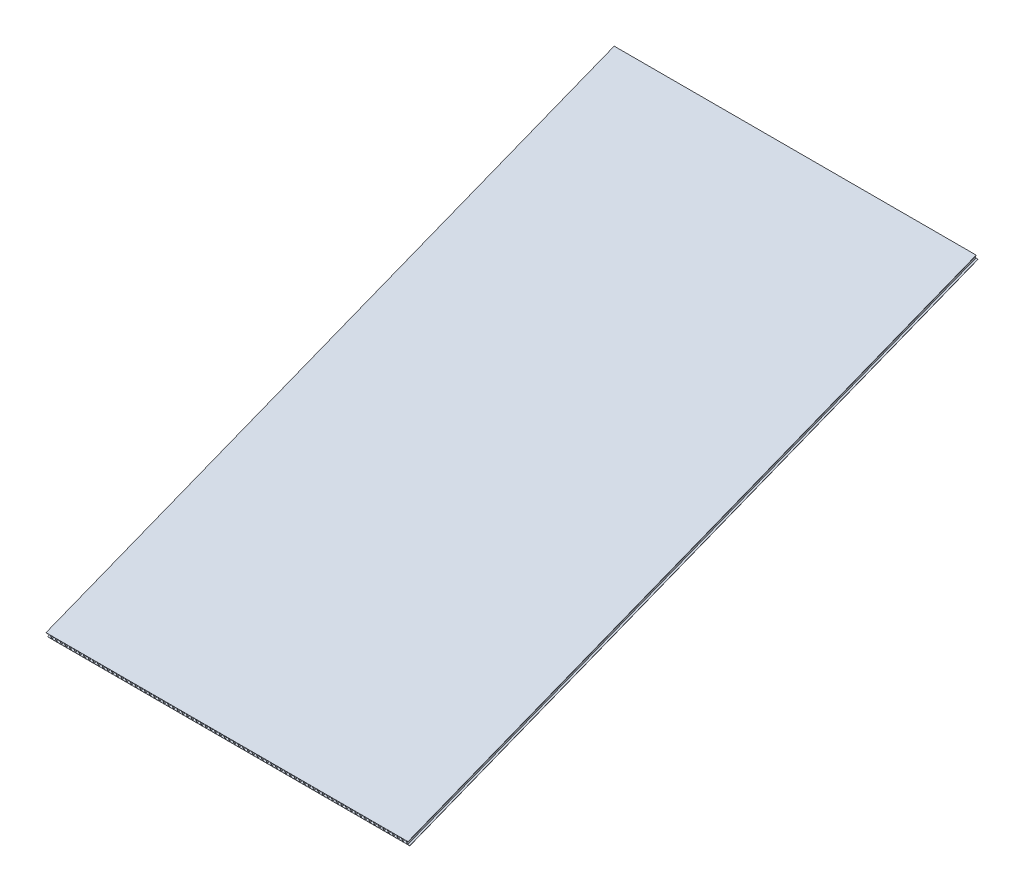
SolidWorks part; units mm, degrees
ref_plane "Front Plane" through (0, 0, 0) normal (0, 0, 1) x (1, 0, 0)
ref_plane "Top Plane" through (0, 0, 0) normal (0, 1, 0) x (1, 0, 0)
ref_plane "Right Plane" through (0, 0, 0) normal (1, 0, 0) x (0, 0, -1)
sketch "Sketch1" plane through (0, 0, 0) normal (1, 0, 0) x (0, 0, -1)
  line L0 (0, 0) -> (-1566.3458, 0) construction
  line L1 (0, 617) -> (-1566.3458, 0)
  line L2 (0, 0) -> (0, 617) construction
  dimension "D1" = 617
  dimension "D2" = 21.5
extrude "Extrude-Thin1" add sketch "Sketch1" along normal blind 1810 thin thin type one direction wall 10
sketch "Sketch2" plane through (0, 82.8774, -210.3965) normal (0, 0.3665, -0.9304) x (-1, 0, 0)
  line L0 (-1810, 584.0676) -> (-1810, 574.0676) construction
  line L1 (-1809.5, 583.5676) -> (-1800.5, 583.5676)
  line L2 (-1809.5, 583.5676) -> (-1809.5, 574.5676)
  line L3 (-1809.5, 574.5676) -> (-1800.5, 574.5676)
  line L4 (-1800.5, 583.5676) -> (-1800.5, 574.5676)
  line L5 (-1810, 584.0676) -> (0, 584.0676) construction
  line L6 (-1810, 574.0676) -> (0, 574.0676) construction
  line L7 (-1791, 583.5676) -> (-1791, 574.5676)
  line L8 (-1800, 574.5676) -> (-1791, 574.5676)
  line L9 (-1800, 583.5676) -> (-1800, 574.5676)
  line L10 (-1800, 583.5676) -> (-1791, 583.5676)
  line L11 (-1781.5, 583.5676) -> (-1781.5, 574.5676)
  line L12 (-1790.5, 574.5676) -> (-1781.5, 574.5676)
  line L13 (-1790.5, 583.5676) -> (-1790.5, 574.5676)
  line L14 (-1790.5, 583.5676) -> (-1781.5, 583.5676)
  line L15 (-1772, 583.5676) -> (-1772, 574.5676)
  line L16 (-1781, 574.5676) -> (-1772, 574.5676)
  line L17 (-1781, 583.5676) -> (-1781, 574.5676)
  line L18 (-1781, 583.5676) -> (-1772, 583.5676)
  line L19 (-1762.5, 583.5676) -> (-1762.5, 574.5676)
  line L20 (-1771.5, 574.5676) -> (-1762.5, 574.5676)
  line L21 (-1771.5, 583.5676) -> (-1771.5, 574.5676)
  line L22 (-1771.5, 583.5676) -> (-1762.5, 583.5676)
  line L23 (-1753, 583.5676) -> (-1753, 574.5676)
  line L24 (-1762, 574.5676) -> (-1753, 574.5676)
  line L25 (-1762, 583.5676) -> (-1762, 574.5676)
  line L26 (-1762, 583.5676) -> (-1753, 583.5676)
  line L27 (-1743.5, 583.5676) -> (-1743.5, 574.5676)
  line L28 (-1752.5, 574.5676) -> (-1743.5, 574.5676)
  line L29 (-1752.5, 583.5676) -> (-1752.5, 574.5676)
  line L30 (-1752.5, 583.5676) -> (-1743.5, 583.5676)
  line L31 (-1734, 583.5676) -> (-1734, 574.5676)
  line L32 (-1743, 574.5676) -> (-1734, 574.5676)
  line L33 (-1743, 583.5676) -> (-1743, 574.5676)
  line L34 (-1743, 583.5676) -> (-1734, 583.5676)
  line L35 (-1724.5, 583.5676) -> (-1724.5, 574.5676)
  line L36 (-1733.5, 574.5676) -> (-1724.5, 574.5676)
  line L37 (-1733.5, 583.5676) -> (-1733.5, 574.5676)
  line L38 (-1733.5, 583.5676) -> (-1724.5, 583.5676)
  line L39 (-1715, 583.5676) -> (-1715, 574.5676)
  line L40 (-1724, 574.5676) -> (-1715, 574.5676)
  line L41 (-1724, 583.5676) -> (-1724, 574.5676)
  line L42 (-1724, 583.5676) -> (-1715, 583.5676)
  line L43 (-1705.5, 583.5676) -> (-1705.5, 574.5676)
  line L44 (-1714.5, 574.5676) -> (-1705.5, 574.5676)
  line L45 (-1714.5, 583.5676) -> (-1714.5, 574.5676)
  line L46 (-1714.5, 583.5676) -> (-1705.5, 583.5676)
  line L47 (-1696, 583.5676) -> (-1696, 574.5676)
  line L48 (-1705, 574.5676) -> (-1696, 574.5676)
  line L49 (-1705, 583.5676) -> (-1705, 574.5676)
  line L50 (-1705, 583.5676) -> (-1696, 583.5676)
  line L51 (-1686.5, 583.5676) -> (-1686.5, 574.5676)
  line L52 (-1695.5, 574.5676) -> (-1686.5, 574.5676)
  line L53 (-1695.5, 583.5676) -> (-1695.5, 574.5676)
  line L54 (-1695.5, 583.5676) -> (-1686.5, 583.5676)
  line L55 (-1677, 583.5676) -> (-1677, 574.5676)
  line L56 (-1686, 574.5676) -> (-1677, 574.5676)
  line L57 (-1686, 583.5676) -> (-1686, 574.5676)
  line L58 (-1686, 583.5676) -> (-1677, 583.5676)
  line L59 (-1667.5, 583.5676) -> (-1667.5, 574.5676)
  line L60 (-1676.5, 574.5676) -> (-1667.5, 574.5676)
  line L61 (-1676.5, 583.5676) -> (-1676.5, 574.5676)
  line L62 (-1676.5, 583.5676) -> (-1667.5, 583.5676)
  line L63 (-1658, 583.5676) -> (-1658, 574.5676)
  line L64 (-1667, 574.5676) -> (-1658, 574.5676)
  line L65 (-1667, 583.5676) -> (-1667, 574.5676)
  line L66 (-1667, 583.5676) -> (-1658, 583.5676)
  line L67 (-1648.5, 583.5676) -> (-1648.5, 574.5676)
  line L68 (-1657.5, 574.5676) -> (-1648.5, 574.5676)
  line L69 (-1657.5, 583.5676) -> (-1657.5, 574.5676)
  line L70 (-1657.5, 583.5676) -> (-1648.5, 583.5676)
  line L71 (-1639, 583.5676) -> (-1639, 574.5676)
  line L72 (-1648, 574.5676) -> (-1639, 574.5676)
  line L73 (-1648, 583.5676) -> (-1648, 574.5676)
  line L74 (-1648, 583.5676) -> (-1639, 583.5676)
  line L75 (-1629.5, 583.5676) -> (-1629.5, 574.5676)
  line L76 (-1638.5, 574.5676) -> (-1629.5, 574.5676)
  line L77 (-1638.5, 583.5676) -> (-1638.5, 574.5676)
  line L78 (-1638.5, 583.5676) -> (-1629.5, 583.5676)
  line L79 (-1620, 583.5676) -> (-1620, 574.5676)
  line L80 (-1629, 574.5676) -> (-1620, 574.5676)
  line L81 (-1629, 583.5676) -> (-1629, 574.5676)
  line L82 (-1629, 583.5676) -> (-1620, 583.5676)
  line L83 (-1610.5, 583.5676) -> (-1610.5, 574.5676)
  line L84 (-1619.5, 574.5676) -> (-1610.5, 574.5676)
  line L85 (-1619.5, 583.5676) -> (-1619.5, 574.5676)
  line L86 (-1619.5, 583.5676) -> (-1610.5, 583.5676)
  line L87 (-1601, 583.5676) -> (-1601, 574.5676)
  line L88 (-1610, 574.5676) -> (-1601, 574.5676)
  line L89 (-1610, 583.5676) -> (-1610, 574.5676)
  line L90 (-1610, 583.5676) -> (-1601, 583.5676)
  line L91 (-1591.5, 583.5676) -> (-1591.5, 574.5676)
  line L92 (-1600.5, 574.5676) -> (-1591.5, 574.5676)
  line L93 (-1600.5, 583.5676) -> (-1600.5, 574.5676)
  line L94 (-1600.5, 583.5676) -> (-1591.5, 583.5676)
  line L95 (-1582, 583.5676) -> (-1582, 574.5676)
  line L96 (-1591, 574.5676) -> (-1582, 574.5676)
  line L97 (-1591, 583.5676) -> (-1591, 574.5676)
  line L98 (-1591, 583.5676) -> (-1582, 583.5676)
  line L99 (-1572.5, 583.5676) -> (-1572.5, 574.5676)
  line L100 (-1581.5, 574.5676) -> (-1572.5, 574.5676)
  line L101 (-1581.5, 583.5676) -> (-1581.5, 574.5676)
  line L102 (-1581.5, 583.5676) -> (-1572.5, 583.5676)
  line L103 (-1563, 583.5676) -> (-1563, 574.5676)
  line L104 (-1572, 574.5676) -> (-1563, 574.5676)
  line L105 (-1572, 583.5676) -> (-1572, 574.5676)
  line L106 (-1572, 583.5676) -> (-1563, 583.5676)
  line L107 (-1553.5, 583.5676) -> (-1553.5, 574.5676)
  line L108 (-1562.5, 574.5676) -> (-1553.5, 574.5676)
  line L109 (-1562.5, 583.5676) -> (-1562.5, 574.5676)
  line L110 (-1562.5, 583.5676) -> (-1553.5, 583.5676)
  line L111 (-1544, 583.5676) -> (-1544, 574.5676)
  line L112 (-1553, 574.5676) -> (-1544, 574.5676)
  line L113 (-1553, 583.5676) -> (-1553, 574.5676)
  line L114 (-1553, 583.5676) -> (-1544, 583.5676)
  line L115 (-1534.5, 583.5676) -> (-1534.5, 574.5676)
  line L116 (-1543.5, 574.5676) -> (-1534.5, 574.5676)
  line L117 (-1543.5, 583.5676) -> (-1543.5, 574.5676)
  line L118 (-1543.5, 583.5676) -> (-1534.5, 583.5676)
  line L119 (-1525, 583.5676) -> (-1525, 574.5676)
  line L120 (-1534, 574.5676) -> (-1525, 574.5676)
  line L121 (-1534, 583.5676) -> (-1534, 574.5676)
  line L122 (-1534, 583.5676) -> (-1525, 583.5676)
  line L123 (-1515.5, 583.5676) -> (-1515.5, 574.5676)
  line L124 (-1524.5, 574.5676) -> (-1515.5, 574.5676)
  line L125 (-1524.5, 583.5676) -> (-1524.5, 574.5676)
  line L126 (-1524.5, 583.5676) -> (-1515.5, 583.5676)
  line L127 (-1506, 583.5676) -> (-1506, 574.5676)
  line L128 (-1515, 574.5676) -> (-1506, 574.5676)
  line L129 (-1515, 583.5676) -> (-1515, 574.5676)
  line L130 (-1515, 583.5676) -> (-1506, 583.5676)
  line L131 (-1496.5, 583.5676) -> (-1496.5, 574.5676)
  line L132 (-1505.5, 574.5676) -> (-1496.5, 574.5676)
  line L133 (-1505.5, 583.5676) -> (-1505.5, 574.5676)
  line L134 (-1505.5, 583.5676) -> (-1496.5, 583.5676)
  line L135 (-1487, 583.5676) -> (-1487, 574.5676)
  line L136 (-1496, 574.5676) -> (-1487, 574.5676)
  line L137 (-1496, 583.5676) -> (-1496, 574.5676)
  line L138 (-1496, 583.5676) -> (-1487, 583.5676)
  line L139 (-1477.5, 583.5676) -> (-1477.5, 574.5676)
  line L140 (-1486.5, 574.5676) -> (-1477.5, 574.5676)
  line L141 (-1486.5, 583.5676) -> (-1486.5, 574.5676)
  line L142 (-1486.5, 583.5676) -> (-1477.5, 583.5676)
  line L143 (-1468, 583.5676) -> (-1468, 574.5676)
  line L144 (-1477, 574.5676) -> (-1468, 574.5676)
  line L145 (-1477, 583.5676) -> (-1477, 574.5676)
  line L146 (-1477, 583.5676) -> (-1468, 583.5676)
  line L147 (-1458.5, 583.5676) -> (-1458.5, 574.5676)
  line L148 (-1467.5, 574.5676) -> (-1458.5, 574.5676)
  line L149 (-1467.5, 583.5676) -> (-1467.5, 574.5676)
  line L150 (-1467.5, 583.5676) -> (-1458.5, 583.5676)
  line L151 (-1449, 583.5676) -> (-1449, 574.5676)
  line L152 (-1458, 574.5676) -> (-1449, 574.5676)
  line L153 (-1458, 583.5676) -> (-1458, 574.5676)
  line L154 (-1458, 583.5676) -> (-1449, 583.5676)
  line L155 (-1439.5, 583.5676) -> (-1439.5, 574.5676)
  line L156 (-1448.5, 574.5676) -> (-1439.5, 574.5676)
  line L157 (-1448.5, 583.5676) -> (-1448.5, 574.5676)
  line L158 (-1448.5, 583.5676) -> (-1439.5, 583.5676)
  line L159 (-1430, 583.5676) -> (-1430, 574.5676)
  line L160 (-1439, 574.5676) -> (-1430, 574.5676)
  line L161 (-1439, 583.5676) -> (-1439, 574.5676)
  line L162 (-1439, 583.5676) -> (-1430, 583.5676)
  line L163 (-1420.5, 583.5676) -> (-1420.5, 574.5676)
  line L164 (-1429.5, 574.5676) -> (-1420.5, 574.5676)
  line L165 (-1429.5, 583.5676) -> (-1429.5, 574.5676)
  line L166 (-1429.5, 583.5676) -> (-1420.5, 583.5676)
  line L167 (-1411, 583.5676) -> (-1411, 574.5676)
  line L168 (-1420, 574.5676) -> (-1411, 574.5676)
  line L169 (-1420, 583.5676) -> (-1420, 574.5676)
  line L170 (-1420, 583.5676) -> (-1411, 583.5676)
  line L171 (-1401.5, 583.5676) -> (-1401.5, 574.5676)
  line L172 (-1410.5, 574.5676) -> (-1401.5, 574.5676)
  line L173 (-1410.5, 583.5676) -> (-1410.5, 574.5676)
  line L174 (-1410.5, 583.5676) -> (-1401.5, 583.5676)
  line L175 (-1392, 583.5676) -> (-1392, 574.5676)
  line L176 (-1401, 574.5676) -> (-1392, 574.5676)
  line L177 (-1401, 583.5676) -> (-1401, 574.5676)
  line L178 (-1401, 583.5676) -> (-1392, 583.5676)
  line L179 (-1382.5, 583.5676) -> (-1382.5, 574.5676)
  line L180 (-1391.5, 574.5676) -> (-1382.5, 574.5676)
  line L181 (-1391.5, 583.5676) -> (-1391.5, 574.5676)
  line L182 (-1391.5, 583.5676) -> (-1382.5, 583.5676)
  line L183 (-1373, 583.5676) -> (-1373, 574.5676)
  line L184 (-1382, 574.5676) -> (-1373, 574.5676)
  line L185 (-1382, 583.5676) -> (-1382, 574.5676)
  line L186 (-1382, 583.5676) -> (-1373, 583.5676)
  line L187 (-1363.5, 583.5676) -> (-1363.5, 574.5676)
  line L188 (-1372.5, 574.5676) -> (-1363.5, 574.5676)
  line L189 (-1372.5, 583.5676) -> (-1372.5, 574.5676)
  line L190 (-1372.5, 583.5676) -> (-1363.5, 583.5676)
  line L191 (-1354, 583.5676) -> (-1354, 574.5676)
  line L192 (-1363, 574.5676) -> (-1354, 574.5676)
  line L193 (-1363, 583.5676) -> (-1363, 574.5676)
  line L194 (-1363, 583.5676) -> (-1354, 583.5676)
  line L195 (-1344.5, 583.5676) -> (-1344.5, 574.5676)
  line L196 (-1353.5, 574.5676) -> (-1344.5, 574.5676)
  line L197 (-1353.5, 583.5676) -> (-1353.5, 574.5676)
  line L198 (-1353.5, 583.5676) -> (-1344.5, 583.5676)
  line L199 (-1335, 583.5676) -> (-1335, 574.5676)
  line L200 (-1344, 574.5676) -> (-1335, 574.5676)
  line L201 (-1344, 583.5676) -> (-1344, 574.5676)
  line L202 (-1344, 583.5676) -> (-1335, 583.5676)
  line L203 (-1325.5, 583.5676) -> (-1325.5, 574.5676)
  line L204 (-1334.5, 574.5676) -> (-1325.5, 574.5676)
  line L205 (-1334.5, 583.5676) -> (-1334.5, 574.5676)
  line L206 (-1334.5, 583.5676) -> (-1325.5, 583.5676)
  line L207 (-1316, 583.5676) -> (-1316, 574.5676)
  line L208 (-1325, 574.5676) -> (-1316, 574.5676)
  line L209 (-1325, 583.5676) -> (-1325, 574.5676)
  line L210 (-1325, 583.5676) -> (-1316, 583.5676)
  line L211 (-1306.5, 583.5676) -> (-1306.5, 574.5676)
  line L212 (-1315.5, 574.5676) -> (-1306.5, 574.5676)
  line L213 (-1315.5, 583.5676) -> (-1315.5, 574.5676)
  line L214 (-1315.5, 583.5676) -> (-1306.5, 583.5676)
  line L215 (-1297, 583.5676) -> (-1297, 574.5676)
  line L216 (-1306, 574.5676) -> (-1297, 574.5676)
  line L217 (-1306, 583.5676) -> (-1306, 574.5676)
  line L218 (-1306, 583.5676) -> (-1297, 583.5676)
  line L219 (-1287.5, 583.5676) -> (-1287.5, 574.5676)
  line L220 (-1296.5, 574.5676) -> (-1287.5, 574.5676)
  line L221 (-1296.5, 583.5676) -> (-1296.5, 574.5676)
  line L222 (-1296.5, 583.5676) -> (-1287.5, 583.5676)
  line L223 (-1278, 583.5676) -> (-1278, 574.5676)
  line L224 (-1287, 574.5676) -> (-1278, 574.5676)
  line L225 (-1287, 583.5676) -> (-1287, 574.5676)
  line L226 (-1287, 583.5676) -> (-1278, 583.5676)
  line L227 (-1268.5, 583.5676) -> (-1268.5, 574.5676)
  line L228 (-1277.5, 574.5676) -> (-1268.5, 574.5676)
  line L229 (-1277.5, 583.5676) -> (-1277.5, 574.5676)
  line L230 (-1277.5, 583.5676) -> (-1268.5, 583.5676)
  line L231 (-1259, 583.5676) -> (-1259, 574.5676)
  line L232 (-1268, 574.5676) -> (-1259, 574.5676)
  line L233 (-1268, 583.5676) -> (-1268, 574.5676)
  line L234 (-1268, 583.5676) -> (-1259, 583.5676)
  line L235 (-1249.5, 583.5676) -> (-1249.5, 574.5676)
  line L236 (-1258.5, 574.5676) -> (-1249.5, 574.5676)
  line L237 (-1258.5, 583.5676) -> (-1258.5, 574.5676)
  line L238 (-1258.5, 583.5676) -> (-1249.5, 583.5676)
  line L239 (-1240, 583.5676) -> (-1240, 574.5676)
  line L240 (-1249, 574.5676) -> (-1240, 574.5676)
  line L241 (-1249, 583.5676) -> (-1249, 574.5676)
  line L242 (-1249, 583.5676) -> (-1240, 583.5676)
  line L243 (-1230.5, 583.5676) -> (-1230.5, 574.5676)
  line L244 (-1239.5, 574.5676) -> (-1230.5, 574.5676)
  line L245 (-1239.5, 583.5676) -> (-1239.5, 574.5676)
  line L246 (-1239.5, 583.5676) -> (-1230.5, 583.5676)
  line L247 (-1221, 583.5676) -> (-1221, 574.5676)
  line L248 (-1230, 574.5676) -> (-1221, 574.5676)
  line L249 (-1230, 583.5676) -> (-1230, 574.5676)
  line L250 (-1230, 583.5676) -> (-1221, 583.5676)
  line L251 (-1211.5, 583.5676) -> (-1211.5, 574.5676)
  line L252 (-1220.5, 574.5676) -> (-1211.5, 574.5676)
  line L253 (-1220.5, 583.5676) -> (-1220.5, 574.5676)
  line L254 (-1220.5, 583.5676) -> (-1211.5, 583.5676)
  line L255 (-1202, 583.5676) -> (-1202, 574.5676)
  line L256 (-1211, 574.5676) -> (-1202, 574.5676)
  line L257 (-1211, 583.5676) -> (-1211, 574.5676)
  line L258 (-1211, 583.5676) -> (-1202, 583.5676)
  line L259 (-1192.5, 583.5676) -> (-1192.5, 574.5676)
  line L260 (-1201.5, 574.5676) -> (-1192.5, 574.5676)
  line L261 (-1201.5, 583.5676) -> (-1201.5, 574.5676)
  line L262 (-1201.5, 583.5676) -> (-1192.5, 583.5676)
  line L263 (-1183, 583.5676) -> (-1183, 574.5676)
  line L264 (-1192, 574.5676) -> (-1183, 574.5676)
  line L265 (-1192, 583.5676) -> (-1192, 574.5676)
  line L266 (-1192, 583.5676) -> (-1183, 583.5676)
  line L267 (-1173.5, 583.5676) -> (-1173.5, 574.5676)
  line L268 (-1182.5, 574.5676) -> (-1173.5, 574.5676)
  line L269 (-1182.5, 583.5676) -> (-1182.5, 574.5676)
  line L270 (-1182.5, 583.5676) -> (-1173.5, 583.5676)
  line L271 (-1164, 583.5676) -> (-1164, 574.5676)
  line L272 (-1173, 574.5676) -> (-1164, 574.5676)
  line L273 (-1173, 583.5676) -> (-1173, 574.5676)
  line L274 (-1173, 583.5676) -> (-1164, 583.5676)
  line L275 (-1154.5, 583.5676) -> (-1154.5, 574.5676)
  line L276 (-1163.5, 574.5676) -> (-1154.5, 574.5676)
  line L277 (-1163.5, 583.5676) -> (-1163.5, 574.5676)
  line L278 (-1163.5, 583.5676) -> (-1154.5, 583.5676)
  line L279 (-1145, 583.5676) -> (-1145, 574.5676)
  line L280 (-1154, 574.5676) -> (-1145, 574.5676)
  line L281 (-1154, 583.5676) -> (-1154, 574.5676)
  line L282 (-1154, 583.5676) -> (-1145, 583.5676)
  line L283 (-1135.5, 583.5676) -> (-1135.5, 574.5676)
  line L284 (-1144.5, 574.5676) -> (-1135.5, 574.5676)
  line L285 (-1144.5, 583.5676) -> (-1144.5, 574.5676)
  line L286 (-1144.5, 583.5676) -> (-1135.5, 583.5676)
  line L287 (-1126, 583.5676) -> (-1126, 574.5676)
  line L288 (-1135, 574.5676) -> (-1126, 574.5676)
  line L289 (-1135, 583.5676) -> (-1135, 574.5676)
  line L290 (-1135, 583.5676) -> (-1126, 583.5676)
  line L291 (-1116.5, 583.5676) -> (-1116.5, 574.5676)
  line L292 (-1125.5, 574.5676) -> (-1116.5, 574.5676)
  line L293 (-1125.5, 583.5676) -> (-1125.5, 574.5676)
  line L294 (-1125.5, 583.5676) -> (-1116.5, 583.5676)
  line L295 (-1107, 583.5676) -> (-1107, 574.5676)
  line L296 (-1116, 574.5676) -> (-1107, 574.5676)
  line L297 (-1116, 583.5676) -> (-1116, 574.5676)
  line L298 (-1116, 583.5676) -> (-1107, 583.5676)
  line L299 (-1097.5, 583.5676) -> (-1097.5, 574.5676)
  line L300 (-1106.5, 574.5676) -> (-1097.5, 574.5676)
  line L301 (-1106.5, 583.5676) -> (-1106.5, 574.5676)
  line L302 (-1106.5, 583.5676) -> (-1097.5, 583.5676)
  line L303 (-1088, 583.5676) -> (-1088, 574.5676)
  line L304 (-1097, 574.5676) -> (-1088, 574.5676)
  line L305 (-1097, 583.5676) -> (-1097, 574.5676)
  line L306 (-1097, 583.5676) -> (-1088, 583.5676)
  line L307 (-1078.5, 583.5676) -> (-1078.5, 574.5676)
  line L308 (-1087.5, 574.5676) -> (-1078.5, 574.5676)
  line L309 (-1087.5, 583.5676) -> (-1087.5, 574.5676)
  line L310 (-1087.5, 583.5676) -> (-1078.5, 583.5676)
  line L311 (-1069, 583.5676) -> (-1069, 574.5676)
  line L312 (-1078, 574.5676) -> (-1069, 574.5676)
  line L313 (-1078, 583.5676) -> (-1078, 574.5676)
  line L314 (-1078, 583.5676) -> (-1069, 583.5676)
  line L315 (-1059.5, 583.5676) -> (-1059.5, 574.5676)
  line L316 (-1068.5, 574.5676) -> (-1059.5, 574.5676)
  line L317 (-1068.5, 583.5676) -> (-1068.5, 574.5676)
  line L318 (-1068.5, 583.5676) -> (-1059.5, 583.5676)
  line L319 (-1050, 583.5676) -> (-1050, 574.5676)
  line L320 (-1059, 574.5676) -> (-1050, 574.5676)
  line L321 (-1059, 583.5676) -> (-1059, 574.5676)
  line L322 (-1059, 583.5676) -> (-1050, 583.5676)
  line L323 (-1040.5, 583.5676) -> (-1040.5, 574.5676)
  line L324 (-1049.5, 574.5676) -> (-1040.5, 574.5676)
  line L325 (-1049.5, 583.5676) -> (-1049.5, 574.5676)
  line L326 (-1049.5, 583.5676) -> (-1040.5, 583.5676)
  line L327 (-1031, 583.5676) -> (-1031, 574.5676)
  line L328 (-1040, 574.5676) -> (-1031, 574.5676)
  line L329 (-1040, 583.5676) -> (-1040, 574.5676)
  line L330 (-1040, 583.5676) -> (-1031, 583.5676)
  line L331 (-1021.5, 583.5676) -> (-1021.5, 574.5676)
  line L332 (-1030.5, 574.5676) -> (-1021.5, 574.5676)
  line L333 (-1030.5, 583.5676) -> (-1030.5, 574.5676)
  line L334 (-1030.5, 583.5676) -> (-1021.5, 583.5676)
  line L335 (-1012, 583.5676) -> (-1012, 574.5676)
  line L336 (-1021, 574.5676) -> (-1012, 574.5676)
  line L337 (-1021, 583.5676) -> (-1021, 574.5676)
  line L338 (-1021, 583.5676) -> (-1012, 583.5676)
  line L339 (-1002.5, 583.5676) -> (-1002.5, 574.5676)
  line L340 (-1011.5, 574.5676) -> (-1002.5, 574.5676)
  line L341 (-1011.5, 583.5676) -> (-1011.5, 574.5676)
  line L342 (-1011.5, 583.5676) -> (-1002.5, 583.5676)
  line L343 (-993, 583.5676) -> (-993, 574.5676)
  line L344 (-1002, 574.5676) -> (-993, 574.5676)
  line L345 (-1002, 583.5676) -> (-1002, 574.5676)
  line L346 (-1002, 583.5676) -> (-993, 583.5676)
  line L347 (-983.5, 583.5676) -> (-983.5, 574.5676)
  line L348 (-992.5, 574.5676) -> (-983.5, 574.5676)
  line L349 (-992.5, 583.5676) -> (-992.5, 574.5676)
  line L350 (-992.5, 583.5676) -> (-983.5, 583.5676)
  line L351 (-974, 583.5676) -> (-974, 574.5676)
  line L352 (-983, 574.5676) -> (-974, 574.5676)
  line L353 (-983, 583.5676) -> (-983, 574.5676)
  line L354 (-983, 583.5676) -> (-974, 583.5676)
  line L355 (-964.5, 583.5676) -> (-964.5, 574.5676)
  line L356 (-973.5, 574.5676) -> (-964.5, 574.5676)
  line L357 (-973.5, 583.5676) -> (-973.5, 574.5676)
  line L358 (-973.5, 583.5676) -> (-964.5, 583.5676)
  line L359 (-955, 583.5676) -> (-955, 574.5676)
  line L360 (-964, 574.5676) -> (-955, 574.5676)
  line L361 (-964, 583.5676) -> (-964, 574.5676)
  line L362 (-964, 583.5676) -> (-955, 583.5676)
  line L363 (-945.5, 583.5676) -> (-945.5, 574.5676)
  line L364 (-954.5, 574.5676) -> (-945.5, 574.5676)
  line L365 (-954.5, 583.5676) -> (-954.5, 574.5676)
  line L366 (-954.5, 583.5676) -> (-945.5, 583.5676)
  line L367 (-936, 583.5676) -> (-936, 574.5676)
  line L368 (-945, 574.5676) -> (-936, 574.5676)
  line L369 (-945, 583.5676) -> (-945, 574.5676)
  line L370 (-945, 583.5676) -> (-936, 583.5676)
  line L371 (-926.5, 583.5676) -> (-926.5, 574.5676)
  line L372 (-935.5, 574.5676) -> (-926.5, 574.5676)
  line L373 (-935.5, 583.5676) -> (-935.5, 574.5676)
  line L374 (-935.5, 583.5676) -> (-926.5, 583.5676)
  line L375 (-917, 583.5676) -> (-917, 574.5676)
  line L376 (-926, 574.5676) -> (-917, 574.5676)
  line L377 (-926, 583.5676) -> (-926, 574.5676)
  line L378 (-926, 583.5676) -> (-917, 583.5676)
  line L379 (-907.5, 583.5676) -> (-907.5, 574.5676)
  line L380 (-916.5, 574.5676) -> (-907.5, 574.5676)
  line L381 (-916.5, 583.5676) -> (-916.5, 574.5676)
  line L382 (-916.5, 583.5676) -> (-907.5, 583.5676)
  line L383 (-898, 583.5676) -> (-898, 574.5676)
  line L384 (-907, 574.5676) -> (-898, 574.5676)
  line L385 (-907, 583.5676) -> (-907, 574.5676)
  line L386 (-907, 583.5676) -> (-898, 583.5676)
  line L387 (-888.5, 583.5676) -> (-888.5, 574.5676)
  line L388 (-897.5, 574.5676) -> (-888.5, 574.5676)
  line L389 (-897.5, 583.5676) -> (-897.5, 574.5676)
  line L390 (-897.5, 583.5676) -> (-888.5, 583.5676)
  line L391 (-879, 583.5676) -> (-879, 574.5676)
  line L392 (-888, 574.5676) -> (-879, 574.5676)
  line L393 (-888, 583.5676) -> (-888, 574.5676)
  line L394 (-888, 583.5676) -> (-879, 583.5676)
  line L395 (-869.5, 583.5676) -> (-869.5, 574.5676)
  line L396 (-878.5, 574.5676) -> (-869.5, 574.5676)
  line L397 (-878.5, 583.5676) -> (-878.5, 574.5676)
  line L398 (-878.5, 583.5676) -> (-869.5, 583.5676)
  line L399 (-860, 583.5676) -> (-860, 574.5676)
  line L400 (-869, 574.5676) -> (-860, 574.5676)
  line L401 (-869, 583.5676) -> (-869, 574.5676)
  line L402 (-869, 583.5676) -> (-860, 583.5676)
  line L403 (-850.5, 583.5676) -> (-850.5, 574.5676)
  line L404 (-859.5, 574.5676) -> (-850.5, 574.5676)
  line L405 (-859.5, 583.5676) -> (-859.5, 574.5676)
  line L406 (-859.5, 583.5676) -> (-850.5, 583.5676)
  line L407 (-841, 583.5676) -> (-841, 574.5676)
  line L408 (-850, 574.5676) -> (-841, 574.5676)
  line L409 (-850, 583.5676) -> (-850, 574.5676)
  line L410 (-850, 583.5676) -> (-841, 583.5676)
  line L411 (-831.5, 583.5676) -> (-831.5, 574.5676)
  line L412 (-840.5, 574.5676) -> (-831.5, 574.5676)
  line L413 (-840.5, 583.5676) -> (-840.5, 574.5676)
  line L414 (-840.5, 583.5676) -> (-831.5, 583.5676)
  line L415 (-822, 583.5676) -> (-822, 574.5676)
  line L416 (-831, 574.5676) -> (-822, 574.5676)
  line L417 (-831, 583.5676) -> (-831, 574.5676)
  line L418 (-831, 583.5676) -> (-822, 583.5676)
  line L419 (-812.5, 583.5676) -> (-812.5, 574.5676)
  line L420 (-821.5, 574.5676) -> (-812.5, 574.5676)
  line L421 (-821.5, 583.5676) -> (-821.5, 574.5676)
  line L422 (-821.5, 583.5676) -> (-812.5, 583.5676)
  line L423 (-803, 583.5676) -> (-803, 574.5676)
  line L424 (-812, 574.5676) -> (-803, 574.5676)
  line L425 (-812, 583.5676) -> (-812, 574.5676)
  line L426 (-812, 583.5676) -> (-803, 583.5676)
  line L427 (-793.5, 583.5676) -> (-793.5, 574.5676)
  line L428 (-802.5, 574.5676) -> (-793.5, 574.5676)
  line L429 (-802.5, 583.5676) -> (-802.5, 574.5676)
  line L430 (-802.5, 583.5676) -> (-793.5, 583.5676)
  line L431 (-784, 583.5676) -> (-784, 574.5676)
  line L432 (-793, 574.5676) -> (-784, 574.5676)
  line L433 (-793, 583.5676) -> (-793, 574.5676)
  line L434 (-793, 583.5676) -> (-784, 583.5676)
  line L435 (-774.5, 583.5676) -> (-774.5, 574.5676)
  line L436 (-783.5, 574.5676) -> (-774.5, 574.5676)
  line L437 (-783.5, 583.5676) -> (-783.5, 574.5676)
  line L438 (-783.5, 583.5676) -> (-774.5, 583.5676)
  line L439 (-765, 583.5676) -> (-765, 574.5676)
  line L440 (-774, 574.5676) -> (-765, 574.5676)
  line L441 (-774, 583.5676) -> (-774, 574.5676)
  line L442 (-774, 583.5676) -> (-765, 583.5676)
  line L443 (-755.5, 583.5676) -> (-755.5, 574.5676)
  line L444 (-764.5, 574.5676) -> (-755.5, 574.5676)
  line L445 (-764.5, 583.5676) -> (-764.5, 574.5676)
  line L446 (-764.5, 583.5676) -> (-755.5, 583.5676)
  line L447 (-746, 583.5676) -> (-746, 574.5676)
  line L448 (-755, 574.5676) -> (-746, 574.5676)
  line L449 (-755, 583.5676) -> (-755, 574.5676)
  line L450 (-755, 583.5676) -> (-746, 583.5676)
  line L451 (-736.5, 583.5676) -> (-736.5, 574.5676)
  line L452 (-745.5, 574.5676) -> (-736.5, 574.5676)
  line L453 (-745.5, 583.5676) -> (-745.5, 574.5676)
  line L454 (-745.5, 583.5676) -> (-736.5, 583.5676)
  line L455 (-727, 583.5676) -> (-727, 574.5676)
  line L456 (-736, 574.5676) -> (-727, 574.5676)
  line L457 (-736, 583.5676) -> (-736, 574.5676)
  line L458 (-736, 583.5676) -> (-727, 583.5676)
  line L459 (-717.5, 583.5676) -> (-717.5, 574.5676)
  line L460 (-726.5, 574.5676) -> (-717.5, 574.5676)
  line L461 (-726.5, 583.5676) -> (-726.5, 574.5676)
  line L462 (-726.5, 583.5676) -> (-717.5, 583.5676)
  line L463 (-708, 583.5676) -> (-708, 574.5676)
  line L464 (-717, 574.5676) -> (-708, 574.5676)
  line L465 (-717, 583.5676) -> (-717, 574.5676)
  line L466 (-717, 583.5676) -> (-708, 583.5676)
  line L467 (-698.5, 583.5676) -> (-698.5, 574.5676)
  line L468 (-707.5, 574.5676) -> (-698.5, 574.5676)
  line L469 (-707.5, 583.5676) -> (-707.5, 574.5676)
  line L470 (-707.5, 583.5676) -> (-698.5, 583.5676)
  line L471 (-689, 583.5676) -> (-689, 574.5676)
  line L472 (-698, 574.5676) -> (-689, 574.5676)
  line L473 (-698, 583.5676) -> (-698, 574.5676)
  line L474 (-698, 583.5676) -> (-689, 583.5676)
  line L475 (-679.5, 583.5676) -> (-679.5, 574.5676)
  line L476 (-688.5, 574.5676) -> (-679.5, 574.5676)
  line L477 (-688.5, 583.5676) -> (-688.5, 574.5676)
  line L478 (-688.5, 583.5676) -> (-679.5, 583.5676)
  line L479 (-670, 583.5676) -> (-670, 574.5676)
  line L480 (-679, 574.5676) -> (-670, 574.5676)
  line L481 (-679, 583.5676) -> (-679, 574.5676)
  line L482 (-679, 583.5676) -> (-670, 583.5676)
  line L483 (-660.5, 583.5676) -> (-660.5, 574.5676)
  line L484 (-669.5, 574.5676) -> (-660.5, 574.5676)
  line L485 (-669.5, 583.5676) -> (-669.5, 574.5676)
  line L486 (-669.5, 583.5676) -> (-660.5, 583.5676)
  line L487 (-651, 583.5676) -> (-651, 574.5676)
  line L488 (-660, 574.5676) -> (-651, 574.5676)
  line L489 (-660, 583.5676) -> (-660, 574.5676)
  line L490 (-660, 583.5676) -> (-651, 583.5676)
  line L491 (-641.5, 583.5676) -> (-641.5, 574.5676)
  line L492 (-650.5, 574.5676) -> (-641.5, 574.5676)
  line L493 (-650.5, 583.5676) -> (-650.5, 574.5676)
  line L494 (-650.5, 583.5676) -> (-641.5, 583.5676)
  line L495 (-632, 583.5676) -> (-632, 574.5676)
  line L496 (-641, 574.5676) -> (-632, 574.5676)
  line L497 (-641, 583.5676) -> (-641, 574.5676)
  line L498 (-641, 583.5676) -> (-632, 583.5676)
  line L499 (-622.5, 583.5676) -> (-622.5, 574.5676)
  line L500 (-631.5, 574.5676) -> (-622.5, 574.5676)
  line L501 (-631.5, 583.5676) -> (-631.5, 574.5676)
  line L502 (-631.5, 583.5676) -> (-622.5, 583.5676)
  line L503 (-613, 583.5676) -> (-613, 574.5676)
  line L504 (-622, 574.5676) -> (-613, 574.5676)
  line L505 (-622, 583.5676) -> (-622, 574.5676)
  line L506 (-622, 583.5676) -> (-613, 583.5676)
  line L507 (-603.5, 583.5676) -> (-603.5, 574.5676)
  line L508 (-612.5, 574.5676) -> (-603.5, 574.5676)
  line L509 (-612.5, 583.5676) -> (-612.5, 574.5676)
  line L510 (-612.5, 583.5676) -> (-603.5, 583.5676)
  line L511 (-594, 583.5676) -> (-594, 574.5676)
  line L512 (-603, 574.5676) -> (-594, 574.5676)
  line L513 (-603, 583.5676) -> (-603, 574.5676)
  line L514 (-603, 583.5676) -> (-594, 583.5676)
  line L515 (-584.5, 583.5676) -> (-584.5, 574.5676)
  line L516 (-593.5, 574.5676) -> (-584.5, 574.5676)
  line L517 (-593.5, 583.5676) -> (-593.5, 574.5676)
  line L518 (-593.5, 583.5676) -> (-584.5, 583.5676)
  line L519 (-575, 583.5676) -> (-575, 574.5676)
  line L520 (-584, 574.5676) -> (-575, 574.5676)
  line L521 (-584, 583.5676) -> (-584, 574.5676)
  line L522 (-584, 583.5676) -> (-575, 583.5676)
  line L523 (-565.5, 583.5676) -> (-565.5, 574.5676)
  line L524 (-574.5, 574.5676) -> (-565.5, 574.5676)
  line L525 (-574.5, 583.5676) -> (-574.5, 574.5676)
  line L526 (-574.5, 583.5676) -> (-565.5, 583.5676)
  line L527 (-556, 583.5676) -> (-556, 574.5676)
  line L528 (-565, 574.5676) -> (-556, 574.5676)
  line L529 (-565, 583.5676) -> (-565, 574.5676)
  line L530 (-565, 583.5676) -> (-556, 583.5676)
  line L531 (-546.5, 583.5676) -> (-546.5, 574.5676)
  line L532 (-555.5, 574.5676) -> (-546.5, 574.5676)
  line L533 (-555.5, 583.5676) -> (-555.5, 574.5676)
  line L534 (-555.5, 583.5676) -> (-546.5, 583.5676)
  line L535 (-537, 583.5676) -> (-537, 574.5676)
  line L536 (-546, 574.5676) -> (-537, 574.5676)
  line L537 (-546, 583.5676) -> (-546, 574.5676)
  line L538 (-546, 583.5676) -> (-537, 583.5676)
  line L539 (-527.5, 583.5676) -> (-527.5, 574.5676)
  line L540 (-536.5, 574.5676) -> (-527.5, 574.5676)
  line L541 (-536.5, 583.5676) -> (-536.5, 574.5676)
  line L542 (-536.5, 583.5676) -> (-527.5, 583.5676)
  line L543 (-518, 583.5676) -> (-518, 574.5676)
  line L544 (-527, 574.5676) -> (-518, 574.5676)
  line L545 (-527, 583.5676) -> (-527, 574.5676)
  line L546 (-527, 583.5676) -> (-518, 583.5676)
  line L547 (-508.5, 583.5676) -> (-508.5, 574.5676)
  line L548 (-517.5, 574.5676) -> (-508.5, 574.5676)
  line L549 (-517.5, 583.5676) -> (-517.5, 574.5676)
  line L550 (-517.5, 583.5676) -> (-508.5, 583.5676)
  line L551 (-499, 583.5676) -> (-499, 574.5676)
  line L552 (-508, 574.5676) -> (-499, 574.5676)
  line L553 (-508, 583.5676) -> (-508, 574.5676)
  line L554 (-508, 583.5676) -> (-499, 583.5676)
  line L555 (-489.5, 583.5676) -> (-489.5, 574.5676)
  line L556 (-498.5, 574.5676) -> (-489.5, 574.5676)
  line L557 (-498.5, 583.5676) -> (-498.5, 574.5676)
  line L558 (-498.5, 583.5676) -> (-489.5, 583.5676)
  line L559 (-480, 583.5676) -> (-480, 574.5676)
  line L560 (-489, 574.5676) -> (-480, 574.5676)
  line L561 (-489, 583.5676) -> (-489, 574.5676)
  line L562 (-489, 583.5676) -> (-480, 583.5676)
  line L563 (-470.5, 583.5676) -> (-470.5, 574.5676)
  line L564 (-479.5, 574.5676) -> (-470.5, 574.5676)
  line L565 (-479.5, 583.5676) -> (-479.5, 574.5676)
  line L566 (-479.5, 583.5676) -> (-470.5, 583.5676)
  line L567 (-461, 583.5676) -> (-461, 574.5676)
  line L568 (-470, 574.5676) -> (-461, 574.5676)
  line L569 (-470, 583.5676) -> (-470, 574.5676)
  line L570 (-470, 583.5676) -> (-461, 583.5676)
  line L571 (-451.5, 583.5676) -> (-451.5, 574.5676)
  line L572 (-460.5, 574.5676) -> (-451.5, 574.5676)
  line L573 (-460.5, 583.5676) -> (-460.5, 574.5676)
  line L574 (-460.5, 583.5676) -> (-451.5, 583.5676)
  line L575 (-442, 583.5676) -> (-442, 574.5676)
  line L576 (-451, 574.5676) -> (-442, 574.5676)
  line L577 (-451, 583.5676) -> (-451, 574.5676)
  line L578 (-451, 583.5676) -> (-442, 583.5676)
  line L579 (-432.5, 583.5676) -> (-432.5, 574.5676)
  line L580 (-441.5, 574.5676) -> (-432.5, 574.5676)
  line L581 (-441.5, 583.5676) -> (-441.5, 574.5676)
  line L582 (-441.5, 583.5676) -> (-432.5, 583.5676)
  line L583 (-423, 583.5676) -> (-423, 574.5676)
  line L584 (-432, 574.5676) -> (-423, 574.5676)
  line L585 (-432, 583.5676) -> (-432, 574.5676)
  line L586 (-432, 583.5676) -> (-423, 583.5676)
  line L587 (-413.5, 583.5676) -> (-413.5, 574.5676)
  line L588 (-422.5, 574.5676) -> (-413.5, 574.5676)
  line L589 (-422.5, 583.5676) -> (-422.5, 574.5676)
  line L590 (-422.5, 583.5676) -> (-413.5, 583.5676)
  line L591 (-404, 583.5676) -> (-404, 574.5676)
  line L592 (-413, 574.5676) -> (-404, 574.5676)
  line L593 (-413, 583.5676) -> (-413, 574.5676)
  line L594 (-413, 583.5676) -> (-404, 583.5676)
  line L595 (-394.5, 583.5676) -> (-394.5, 574.5676)
  line L596 (-403.5, 574.5676) -> (-394.5, 574.5676)
  line L597 (-403.5, 583.5676) -> (-403.5, 574.5676)
  line L598 (-403.5, 583.5676) -> (-394.5, 583.5676)
  line L599 (-385, 583.5676) -> (-385, 574.5676)
  line L600 (-394, 574.5676) -> (-385, 574.5676)
  line L601 (-394, 583.5676) -> (-394, 574.5676)
  line L602 (-394, 583.5676) -> (-385, 583.5676)
  line L603 (-375.5, 583.5676) -> (-375.5, 574.5676)
  line L604 (-384.5, 574.5676) -> (-375.5, 574.5676)
  line L605 (-384.5, 583.5676) -> (-384.5, 574.5676)
  line L606 (-384.5, 583.5676) -> (-375.5, 583.5676)
  line L607 (-366, 583.5676) -> (-366, 574.5676)
  line L608 (-375, 574.5676) -> (-366, 574.5676)
  line L609 (-375, 583.5676) -> (-375, 574.5676)
  line L610 (-375, 583.5676) -> (-366, 583.5676)
  line L611 (-356.5, 583.5676) -> (-356.5, 574.5676)
  line L612 (-365.5, 574.5676) -> (-356.5, 574.5676)
  line L613 (-365.5, 583.5676) -> (-365.5, 574.5676)
  line L614 (-365.5, 583.5676) -> (-356.5, 583.5676)
  line L615 (-347, 583.5676) -> (-347, 574.5676)
  line L616 (-356, 574.5676) -> (-347, 574.5676)
  line L617 (-356, 583.5676) -> (-356, 574.5676)
  line L618 (-356, 583.5676) -> (-347, 583.5676)
  line L619 (-337.5, 583.5676) -> (-337.5, 574.5676)
  line L620 (-346.5, 574.5676) -> (-337.5, 574.5676)
  line L621 (-346.5, 583.5676) -> (-346.5, 574.5676)
  line L622 (-346.5, 583.5676) -> (-337.5, 583.5676)
  line L623 (-328, 583.5676) -> (-328, 574.5676)
  line L624 (-337, 574.5676) -> (-328, 574.5676)
  line L625 (-337, 583.5676) -> (-337, 574.5676)
  line L626 (-337, 583.5676) -> (-328, 583.5676)
  line L627 (-318.5, 583.5676) -> (-318.5, 574.5676)
  line L628 (-327.5, 574.5676) -> (-318.5, 574.5676)
  line L629 (-327.5, 583.5676) -> (-327.5, 574.5676)
  line L630 (-327.5, 583.5676) -> (-318.5, 583.5676)
  line L631 (-309, 583.5676) -> (-309, 574.5676)
  line L632 (-318, 574.5676) -> (-309, 574.5676)
  line L633 (-318, 583.5676) -> (-318, 574.5676)
  line L634 (-318, 583.5676) -> (-309, 583.5676)
  line L635 (-299.5, 583.5676) -> (-299.5, 574.5676)
  line L636 (-308.5, 574.5676) -> (-299.5, 574.5676)
  line L637 (-308.5, 583.5676) -> (-308.5, 574.5676)
  line L638 (-308.5, 583.5676) -> (-299.5, 583.5676)
  line L639 (-290, 583.5676) -> (-290, 574.5676)
  line L640 (-299, 574.5676) -> (-290, 574.5676)
  line L641 (-299, 583.5676) -> (-299, 574.5676)
  line L642 (-299, 583.5676) -> (-290, 583.5676)
  line L643 (-280.5, 583.5676) -> (-280.5, 574.5676)
  line L644 (-289.5, 574.5676) -> (-280.5, 574.5676)
  line L645 (-289.5, 583.5676) -> (-289.5, 574.5676)
  line L646 (-289.5, 583.5676) -> (-280.5, 583.5676)
  line L647 (-271, 583.5676) -> (-271, 574.5676)
  line L648 (-280, 574.5676) -> (-271, 574.5676)
  line L649 (-280, 583.5676) -> (-280, 574.5676)
  line L650 (-280, 583.5676) -> (-271, 583.5676)
  line L651 (-261.5, 583.5676) -> (-261.5, 574.5676)
  line L652 (-270.5, 574.5676) -> (-261.5, 574.5676)
  line L653 (-270.5, 583.5676) -> (-270.5, 574.5676)
  line L654 (-270.5, 583.5676) -> (-261.5, 583.5676)
  line L655 (-252, 583.5676) -> (-252, 574.5676)
  line L656 (-261, 574.5676) -> (-252, 574.5676)
  line L657 (-261, 583.5676) -> (-261, 574.5676)
  line L658 (-261, 583.5676) -> (-252, 583.5676)
  line L659 (-242.5, 583.5676) -> (-242.5, 574.5676)
  line L660 (-251.5, 574.5676) -> (-242.5, 574.5676)
  line L661 (-251.5, 583.5676) -> (-251.5, 574.5676)
  line L662 (-251.5, 583.5676) -> (-242.5, 583.5676)
  line L663 (-233, 583.5676) -> (-233, 574.5676)
  line L664 (-242, 574.5676) -> (-233, 574.5676)
  line L665 (-242, 583.5676) -> (-242, 574.5676)
  line L666 (-242, 583.5676) -> (-233, 583.5676)
  line L667 (-223.5, 583.5676) -> (-223.5, 574.5676)
  line L668 (-232.5, 574.5676) -> (-223.5, 574.5676)
  line L669 (-232.5, 583.5676) -> (-232.5, 574.5676)
  line L670 (-232.5, 583.5676) -> (-223.5, 583.5676)
  line L671 (-214, 583.5676) -> (-214, 574.5676)
  line L672 (-223, 574.5676) -> (-214, 574.5676)
  line L673 (-223, 583.5676) -> (-223, 574.5676)
  line L674 (-223, 583.5676) -> (-214, 583.5676)
  line L675 (-204.5, 583.5676) -> (-204.5, 574.5676)
  line L676 (-213.5, 574.5676) -> (-204.5, 574.5676)
  line L677 (-213.5, 583.5676) -> (-213.5, 574.5676)
  line L678 (-213.5, 583.5676) -> (-204.5, 583.5676)
  line L679 (-195, 583.5676) -> (-195, 574.5676)
  line L680 (-204, 574.5676) -> (-195, 574.5676)
  line L681 (-204, 583.5676) -> (-204, 574.5676)
  line L682 (-204, 583.5676) -> (-195, 583.5676)
  line L683 (-185.5, 583.5676) -> (-185.5, 574.5676)
  line L684 (-194.5, 574.5676) -> (-185.5, 574.5676)
  line L685 (-194.5, 583.5676) -> (-194.5, 574.5676)
  line L686 (-194.5, 583.5676) -> (-185.5, 583.5676)
  line L687 (-176, 583.5676) -> (-176, 574.5676)
  line L688 (-185, 574.5676) -> (-176, 574.5676)
  line L689 (-185, 583.5676) -> (-185, 574.5676)
  line L690 (-185, 583.5676) -> (-176, 583.5676)
  line L691 (-166.5, 583.5676) -> (-166.5, 574.5676)
  line L692 (-175.5, 574.5676) -> (-166.5, 574.5676)
  line L693 (-175.5, 583.5676) -> (-175.5, 574.5676)
  line L694 (-175.5, 583.5676) -> (-166.5, 583.5676)
  line L695 (-157, 583.5676) -> (-157, 574.5676)
  line L696 (-166, 574.5676) -> (-157, 574.5676)
  line L697 (-166, 583.5676) -> (-166, 574.5676)
  line L698 (-166, 583.5676) -> (-157, 583.5676)
  line L699 (-147.5, 583.5676) -> (-147.5, 574.5676)
  line L700 (-156.5, 574.5676) -> (-147.5, 574.5676)
  line L701 (-156.5, 583.5676) -> (-156.5, 574.5676)
  line L702 (-156.5, 583.5676) -> (-147.5, 583.5676)
  line L703 (-138, 583.5676) -> (-138, 574.5676)
  line L704 (-147, 574.5676) -> (-138, 574.5676)
  line L705 (-147, 583.5676) -> (-147, 574.5676)
  line L706 (-147, 583.5676) -> (-138, 583.5676)
  line L707 (-128.5, 583.5676) -> (-128.5, 574.5676)
  line L708 (-137.5, 574.5676) -> (-128.5, 574.5676)
  line L709 (-137.5, 583.5676) -> (-137.5, 574.5676)
  line L710 (-137.5, 583.5676) -> (-128.5, 583.5676)
  line L711 (-119, 583.5676) -> (-119, 574.5676)
  line L712 (-128, 574.5676) -> (-119, 574.5676)
  line L713 (-128, 583.5676) -> (-128, 574.5676)
  line L714 (-128, 583.5676) -> (-119, 583.5676)
  line L715 (-109.5, 583.5676) -> (-109.5, 574.5676)
  line L716 (-118.5, 574.5676) -> (-109.5, 574.5676)
  line L717 (-118.5, 583.5676) -> (-118.5, 574.5676)
  line L718 (-118.5, 583.5676) -> (-109.5, 583.5676)
  line L719 (-100, 583.5676) -> (-100, 574.5676)
  line L720 (-109, 574.5676) -> (-100, 574.5676)
  line L721 (-109, 583.5676) -> (-109, 574.5676)
  line L722 (-109, 583.5676) -> (-100, 583.5676)
  line L723 (-90.5, 583.5676) -> (-90.5, 574.5676)
  line L724 (-99.5, 574.5676) -> (-90.5, 574.5676)
  line L725 (-99.5, 583.5676) -> (-99.5, 574.5676)
  line L726 (-99.5, 583.5676) -> (-90.5, 583.5676)
  line L727 (-81, 583.5676) -> (-81, 574.5676)
  line L728 (-90, 574.5676) -> (-81, 574.5676)
  line L729 (-90, 583.5676) -> (-90, 574.5676)
  line L730 (-90, 583.5676) -> (-81, 583.5676)
  line L731 (-71.5, 583.5676) -> (-71.5, 574.5676)
  line L732 (-80.5, 574.5676) -> (-71.5, 574.5676)
  line L733 (-80.5, 583.5676) -> (-80.5, 574.5676)
  line L734 (-80.5, 583.5676) -> (-71.5, 583.5676)
  line L735 (-62, 583.5676) -> (-62, 574.5676)
  line L736 (-71, 574.5676) -> (-62, 574.5676)
  line L737 (-71, 583.5676) -> (-71, 574.5676)
  line L738 (-71, 583.5676) -> (-62, 583.5676)
  line L739 (-52.5, 583.5676) -> (-52.5, 574.5676)
  line L740 (-61.5, 574.5676) -> (-52.5, 574.5676)
  line L741 (-61.5, 583.5676) -> (-61.5, 574.5676)
  line L742 (-61.5, 583.5676) -> (-52.5, 583.5676)
  line L743 (-43, 583.5676) -> (-43, 574.5676)
  line L744 (-52, 574.5676) -> (-43, 574.5676)
  line L745 (-52, 583.5676) -> (-52, 574.5676)
  line L746 (-52, 583.5676) -> (-43, 583.5676)
  line L747 (-33.5, 583.5676) -> (-33.5, 574.5676)
  line L748 (-42.5, 574.5676) -> (-33.5, 574.5676)
  line L749 (-42.5, 583.5676) -> (-42.5, 574.5676)
  line L750 (-42.5, 583.5676) -> (-33.5, 583.5676)
  line L751 (-24, 583.5676) -> (-24, 574.5676)
  line L752 (-33, 574.5676) -> (-24, 574.5676)
  line L753 (-33, 583.5676) -> (-33, 574.5676)
  line L754 (-33, 583.5676) -> (-24, 583.5676)
  line L755 (-14.5, 583.5676) -> (-14.5, 574.5676)
  line L756 (-23.5, 574.5676) -> (-14.5, 574.5676)
  line L757 (-23.5, 583.5676) -> (-23.5, 574.5676)
  line L758 (-23.5, 583.5676) -> (-14.5, 583.5676)
  line L759 (-5, 583.5676) -> (-5, 574.5676)
  line L760 (-14, 574.5676) -> (-5, 574.5676)
  line L761 (-14, 583.5676) -> (-14, 574.5676)
  line L762 (-14, 583.5676) -> (-5, 583.5676)
  line L763 (4.5, 583.5676) -> (4.5, 574.5676)
  line L764 (-4.5, 574.5676) -> (4.5, 574.5676)
  line L765 (-4.5, 583.5676) -> (-4.5, 574.5676)
  line L766 (-4.5, 583.5676) -> (4.5, 583.5676)
  dimension "D1" = 0.5
  dimension "D2" = 0.5
  dimension "D3" = 0.5
  dimension "D4" = 191
extrude "Cut-Extrude1" cut sketch "Sketch2" against normal through all
sketch "Sketch3" plane through (0, 543.4268, 214.0615) normal (0, 0.9304, 0.3665) x (1, 0, 0)
  line L1 (119.414, 35.6484) -> (854.414, 35.6484)
  line L2 (119.414, 35.6484) -> (119.414, -1204.3516)
  line L3 (119.414, -1204.3516) -> (854.414, -1204.3516)
  line L4 (854.414, 35.6484) -> (854.414, -1204.3516)
  line L5 (2055.2881, 390.3564) -> (-326.4601, 390.3564)
  line L6 (2055.2881, 390.3564) -> (2055.2881, -1726.8125)
  line L7 (2055.2881, -1726.8125) -> (-326.4601, -1726.8125)
  line L8 (-326.4601, 390.3564) -> (-326.4601, -1726.8125)
  line L9 (2055.2881, 390.3564) -> (-326.4601, -1726.8125) construction
  line L10 (2055.2881, -1726.8125) -> (-326.4601, 390.3564) construction
  point P4 (864.414, -668.2281)
  dimension "D1" = 735
  dimension "D2" = 1240
  dimension "D3" = 10
extrude "Cut-Extrude2" cut sketch "Sketch3" against normal through all
